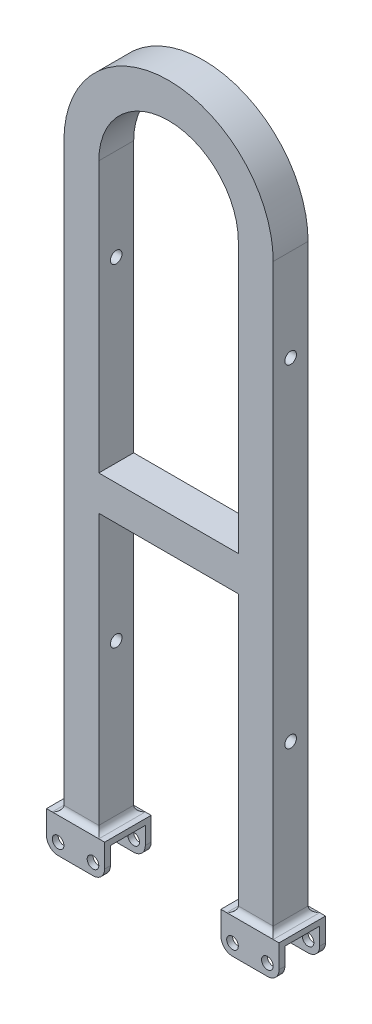
SolidWorks part; units mm, degrees
ref_plane "Front Plane" through (0, 0, 0) normal (0, 0, 1) x (1, 0, 0)
ref_plane "Top Plane" through (0, 0, 0) normal (0, 1, 0) x (1, 0, 0)
ref_plane "Right Plane" through (0, 0, 0) normal (1, 0, 0) x (0, 0, -1)
sketch "Sketch1" plane through (0, 0, 0) normal (0, 0, 1) x (1, 0, 0)
  line L0 (-206.8046, 0) -> (222.9062, 0) construction
  line L1 (222.9062, 0) -> (0, 0) construction
  line L2 (0, 0) -> (0, 156.9904) construction
  line L3 (-75, 42.2835) -> (-75, -37.5029) construction
  line L4 (75, 42.2835) -> (75, -37.5029) construction
  line L5 (-90, 17.5) -> (-90, 517.5)
  line L6 (-60, -17.5) -> (-90, -17.5)
  line L7 (-50, -7.5) -> (-50, 17.5)
  line L8 (-50, 17.5) -> (-60, 17.5)
  line L9 (-100, -7.5) -> (-100, 17.5)
  line L10 (-60, 17.5) -> (-60, 517.5)
  line L11 (-90, 17.5) -> (-100, 17.5)
  line L13 (-60, 17.5) -> (-50, 17.5)
  line L14 (-90, 17.5) -> (-90, 517.5)
  line L15 (-50, -7.5) -> (-50, 17.5)
  line L16 (-100, 17.5) -> (-90, 17.5)
  line L17 (-100, -7.5) -> (-100, 17.5)
  line L18 (-60, 17.5) -> (-60, 517.5)
  line L19 (75, 42.2835) -> (75, -37.5029) construction
  line L20 (60, 17.5) -> (60, 517.5)
  line L21 (100, -7.5) -> (100, 17.5)
  line L22 (100, 17.5) -> (90, 17.5)
  line L23 (50, -7.5) -> (50, 17.5)
  line L24 (90, 17.5) -> (90, 517.5)
  line L25 (60, 17.5) -> (50, 17.5)
  line L27 (90, 17.5) -> (100, 17.5)
  line L28 (60, 17.5) -> (60, 517.5)
  line L29 (100, -7.5) -> (100, 17.5)
  line L30 (50, 17.5) -> (60, 17.5)
  line L31 (50, -7.5) -> (50, 17.5)
  line L32 (60, -17.5) -> (90, -17.5)
  line L33 (90, 17.5) -> (90, 517.5)
  circle A0 centre (-90, -7.5) radius 5
  arc A1 (-50, -7.5) -> (-60, -17.5) centre (-60, -7.5) cw
  arc A2 (-90, -17.5) -> (-100, -7.5) centre (-90, -7.5) cw
  circle A3 centre (-60, -7.5) radius 5
  circle A4 centre (-90, -7.5) radius 5
  arc A5 (-60, -17.5) -> (-50, -7.5) centre (-60, -7.5) ccw
  arc A6 (-100, -7.5) -> (-90, -17.5) centre (-90, -7.5) ccw
  circle A7 centre (-60, -7.5) radius 5
  circle A8 centre (60, -7.5) radius 5
  arc A9 (100, -7.5) -> (90, -17.5) centre (90, -7.5) cw
  arc A10 (60, -17.5) -> (50, -7.5) centre (60, -7.5) cw
  circle A11 centre (90, -7.5) radius 5
  circle A12 centre (60, -7.5) radius 5
  arc A13 (90, -17.5) -> (100, -7.5) centre (90, -7.5) ccw
  arc A14 (50, -7.5) -> (60, -17.5) centre (60, -7.5) ccw
  circle A15 centre (90, -7.5) radius 5
  arc A16 (60, 517.5) -> (-60, 517.5) centre (0, 517.5) ccw
  arc A17 (90, 517.5) -> (-90, 517.5) centre (0, 517.5) ccw
  point P9 (-75, 0)
  point P20 (-100, -17.5)
  point P44 (100, -17.5)
  point P45 (75, 0)
  dimension "D4" = 500
  dimension "D5" = 15
  dimension "D6" = 10
  dimension "D1" = 75
  dimension "D2" = 50
  dimension "D3" = 35
extrude "Boss-Extrude1" add sketch "Sketch1" along normal blind 50 contours L24 A17 L5 L11 L9 A2 L6 A1 L7 L8 L10 A16 L20 L25 L23 A10 L32 A9 L21 L22 A11 A8 A0 A3 region at (-83.4378, 267.5, 0)
sketch "Sketch2" plane through (90, 0, 0) normal (1, 0, 0) x (0, 0, -1)
  line L0 (0, 607.5) -> (-50, 607.5) construction
  line L1 (-50, 17.5) -> (-45, 17.5)
  line L2 (-50, 17.5) -> (-50, 607.5)
  line L3 (-50, 607.5) -> (-40, 607.5)
  line L4 (-40, 22.5) -> (-40, 607.5)
  line L5 (-50, -17.5) -> (0, -17.5) construction
  line L6 (-40, -17.5) -> (-10, -17.5)
  line L7 (-40, -17.5) -> (-40, 12.5)
  line L8 (-40, 12.5) -> (-10, 12.5)
  line L9 (-10, -17.5) -> (-10, 12.5)
  line L10 (-50, 17.5) -> (0, 17.5) construction
  line L11 (-5, 17.5) -> (0, 17.5)
  line L12 (-10, 22.5) -> (-10, 607.5)
  line L13 (-10, 607.5) -> (0, 607.5)
  line L14 (0, 17.5) -> (0, 607.5)
  line L15 (0, 517.5) -> (0, 607.5) construction
  arc A0 (-5, 17.5) -> (-10, 22.5) centre (-5, 22.5) cw
  arc A1 (-45, 17.5) -> (-40, 22.5) centre (-45, 22.5) ccw
  point P23 (-10, 17.5)
  dimension "D4" = 5
  dimension "D1" = 10
  dimension "D2" = 30
  dimension "D3" = 30
extrude "Cut-Extrude1" cut sketch "Sketch2" against normal through all
sketch "Sketch3" plane through (100, 0, 0) normal (1, 0, 0) x (0, 0, -1)
  line L0 (-50, 17.5) -> (0, 17.5) construction
  line L1 (-10, -17.5) -> (-40, -17.5)
  line L2 (-10, -17.5) -> (-10, 12.5)
  line L3 (-10, 12.5) -> (-40, 12.5)
  line L4 (-40, -17.5) -> (-40, 12.5)
  line L5 (-50, 17.5) -> (-45, 17.5)
  line L6 (-50, 17.5) -> (-50, -17.5)
  line L7 (-50, -17.5) -> (-45, -17.5)
  line L8 (-45, 17.5) -> (-45, -17.5)
  line L9 (0, -17.5) -> (-5, -17.5)
  line L10 (0, -17.5) -> (0, 17.5)
  line L11 (0, 17.5) -> (-5, 17.5)
  line L12 (-5, -17.5) -> (-5, 17.5)
  dimension "D1" = 30
  dimension "D2" = 5
  dimension "D3" = 5
  dimension "D4" = 5
extrude "Cut-Extrude2" cut sketch "Sketch3" against normal through all
fillet "Fillet1" radius 5 4 edges at (-90, 17.5, 25) (60, 17.5, 25) (-60, 17.5, 25) (90, 17.5, 25)
sketch "Sketch4" plane through (90, 0, 0) normal (1, 0, 0) x (0, 0, -1)
  line L0 (-25, 22.5) -> (-25, 263.4863) construction
  line L1 (-40, 22.5) -> (-10, 22.5) construction
  line L3 (55.6873, 152.5) -> (-65.8716, 152.5) construction
  circle A0 centre (-25, 152.5) radius 5
  dimension "D1" = 130
extrude "Cut-Extrude3" cut sketch "Sketch4" against normal through all
sketch "Sketch5" plane through (-60, 0, 0) normal (1, 0, 0) x (0, 0, -1)
  line L0 (-40, 517.5) -> (-40, 22.5) construction
  line L1 (-40, 285) -> (-10, 285)
  line L2 (-40, 285) -> (-40, 255)
  line L3 (-40, 255) -> (-10, 255)
  line L4 (-10, 285) -> (-10, 255)
  line L5 (-10, 22.5) -> (-10, 517.5) construction
  line L6 (-40, 270) -> (-10, 270) construction
  line L7 (-10, 270) -> (-25, 270) construction
  dimension "D1" = 30
  dimension "D2" = 15
extrude "Boss-Extrude2" add sketch "Sketch5" along normal blind 120
sketch "Sketch6" plane through (100, 0, 0) normal (1, 0, 0) x (0, 0, -1)
  line L1 (-45, 17.5) -> (-3.1189, 17.5)
  line L2 (-45, 17.5) -> (-45, -21.0984)
  line L3 (-45, -21.0984) -> (-3.1189, -21.0984)
  line L4 (-3.1189, 17.5) -> (-3.1189, -21.0984)
extrude "Cut-Extrude4" cut sketch "Sketch6" against normal through all
sketch "Sketch7" plane through (0, 17.5, 0) normal (0, -1, 0) x (1, 0, 0)
  line L1 (-50, 5) -> (-100, 5)
  line L2 (-50, 5) -> (-50, 45)
  line L3 (-50, 45) -> (-100, 45)
  line L4 (-100, 5) -> (-100, 45)
  line L5 (-50, 5) -> (-100, 45) construction
  line L6 (-50, 45) -> (-100, 5) construction
  line L7 (-95, 45) -> (-55, 45) construction
  line L8 (-95, 45) -> (-95, 5) construction
  line L9 (0, 0) -> (0, 58.2628) construction
  line L10 (50, 45) -> (100, 45)
  line L11 (100, 5) -> (100, 45)
  line L12 (50, 5) -> (100, 5)
  line L13 (50, 5) -> (50, 45)
  point P0 (-75, 25)
  dimension "D1" = 40
  dimension "D2" = 50
  dimension "D3" = 5
extrude "Boss-Extrude3" add sketch "Sketch7" along normal blind 30
sketch "Sketch8" plane through (0, 0, 45) normal (0, 0, 1) x (1, 0, 0)
  line L0 (0, 61.6339) -> (0, 0) construction
  line L1 (0, 0) -> (-50, 0) construction
  line L4 (-100, -2.5) -> (-100, 17.5)
  line L6 (-50, -2.5) -> (-50, 0)
  line L8 (-75, -2.5) -> (-75, 0) construction
  line L9 (-100, -2.5) -> (-50, -2.5) construction
  line L10 (100, -2.5) -> (85, -2.5) construction
  line L15 (90, -12.5) -> (75, -12.5)
  line L16 (65, -2.5) -> (50, -2.5) construction
  circle A0 centre (-90, -2.5) radius 5
  circle A1 centre (-60, -2.5) radius 5
  circle A6 centre (60, -2.5) radius 5
  circle A7 centre (90, -2.5) radius 5
  point P25 (-100, -12.5)
  point P38 (100, -12.5)
  dimension "D2" = 15
extrude "Cut-Extrude5" cut sketch "Sketch8" against normal through all contours A0 | A1 | A6 | A7 region at (-90, -2.5, 45) region at (-60, -2.5, 45) region at (60, -2.5, 45) region at (90, -2.5, 45)
fillet "Fillet2" radius 10 4 edges at (50, -12.5, 25) (-100, -12.5, 25) (-50, -12.5, 25) (100, -12.5, 25)
sketch "Sketch9" plane through (-100, 0, 0) normal (-1, 0, 0) x (0, 0, 1)
  line L0 (45, -12.5) -> (5, -12.5) construction
  line L1 (10, -12.5) -> (40, -12.5)
  line L2 (10, -12.5) -> (10, 12.5)
  line L3 (10, 12.5) -> (40, 12.5)
  line L4 (40, -12.5) -> (40, 12.5)
  line L5 (5, -2.5) -> (5, 17.5) construction
  dimension "D1" = 5
  dimension "D2" = 30
  dimension "D3" = 25
extrude "Cut-Extrude6" cut sketch "Sketch9" against normal through all
sketch "Sketch10" plane through (-90, 0, 0) normal (-1, 0, 0) x (0, 0, 1)
  circle A0 centre (25, 438.2965) radius 5
  dimension "D1" = 10
extrude "Cut-Extrude7" cut sketch "Sketch10" against normal through all both and the other way through all
